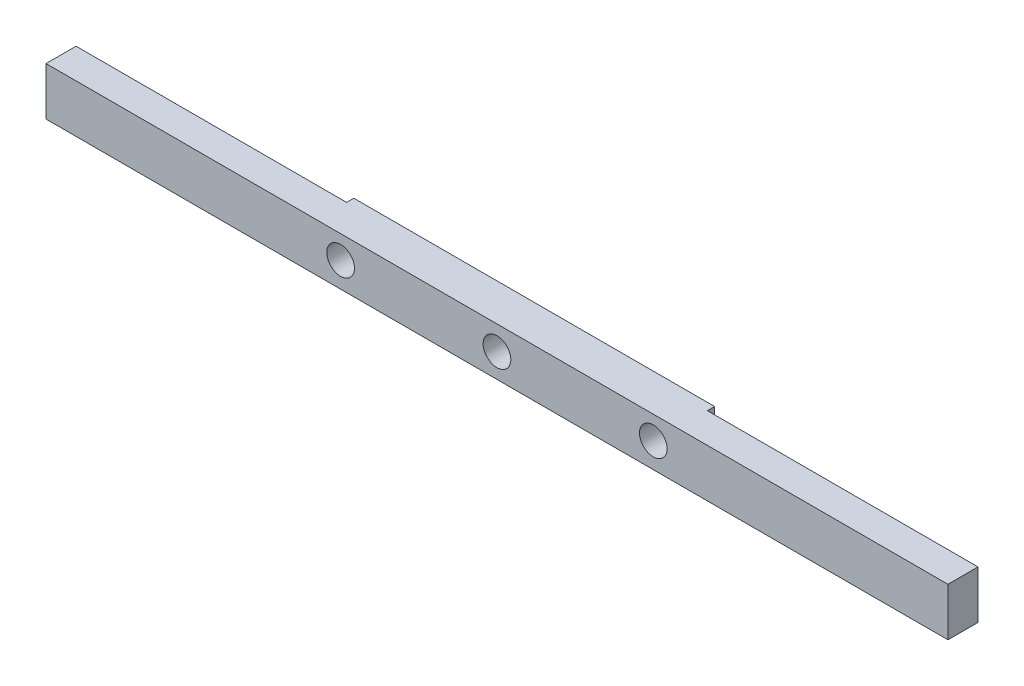
SolidWorks part; units mm, degrees
ref_plane "Front Plane" through (0, 0, 0) normal (0, 0, 1) x (1, 0, 0)
ref_plane "Top Plane" through (0, 0, 0) normal (0, 1, 0) x (1, 0, 0)
ref_plane "Right Plane" through (0, 0, 0) normal (1, 0, 0) x (0, 0, -1)
sketch "Sketch1" plane through (0, 0, 0) normal (0, 0, 1) x (1, 0, 0)
  line L1 (0, 0) -> (75, 0)
  line L2 (0, 0) -> (0, 4)
  line L3 (0, 4) -> (75, 4)
  line L4 (75, 0) -> (75, 4)
  dimension "D1" = 4
  dimension "D2" = 75
extrude "Boss-Extrude1" add sketch "Sketch1" along normal blind 2.5
sketch "Sketch2" plane through (0, 0, 0) normal (0, 0, -1) x (-1, 0, 0)
  line L0 (0, 0) -> (-75, 4) construction
  line L1 (-75, 4) -> (-75, 0) construction
  line L2 (-75, 0) -> (0, 4) construction
  circle A0 centre (-37.5, 2) radius 1.15
  dimension "D1" = 2.3
extrude "Cut-Extrude1" cut sketch "Sketch2" against normal blind 3
sketch "Sketch3" plane through (0, 0, 0) normal (0, 0, -1) x (-1, 0, 0)
  line L0 (0, 0) -> (-75, 0) construction
  line L1 (-22.5, 0) -> (-52.5, 0)
  line L2 (-22.5, 0) -> (-22.5, 4)
  line L3 (-22.5, 4) -> (-52.5, 4)
  line L4 (-52.5, 0) -> (-52.5, 4)
  line L5 (-75, 4) -> (0, 4) construction
  circle A0 centre (-37.5, 2) radius 1.15 construction
  dimension "D1" = 15
  dimension "D2" = 15
extrude "Boss-Extrude2" add sketch "Sketch3" along normal blind 0.6
extrude "Cut-Extrude2" cut sketch "Sketch2<2>" along normal through all
sketch "Sketch2<2>" plane through (0, 0, 0) normal (0, 0, -1) x (-1, 0, 0) same geometry as "Sketch2"
sketch "Sketch4" plane through (0, 0, 2.5) normal (0, 0, 1) x (1, 0, 0)
  circle A0 centre (24.5, 2.0765) radius 1.15
  circle A1 centre (50.5, 2.0765) radius 1.15
  circle A2 centre (37.5, 2) radius 1.15 construction
  dimension "D1" = 13
  dimension "D2" = 13
  dimension "D3" = 2.3
  dimension "D4" = 2.3
extrude "Cut-Extrude3" cut sketch "Sketch4" against normal through all
